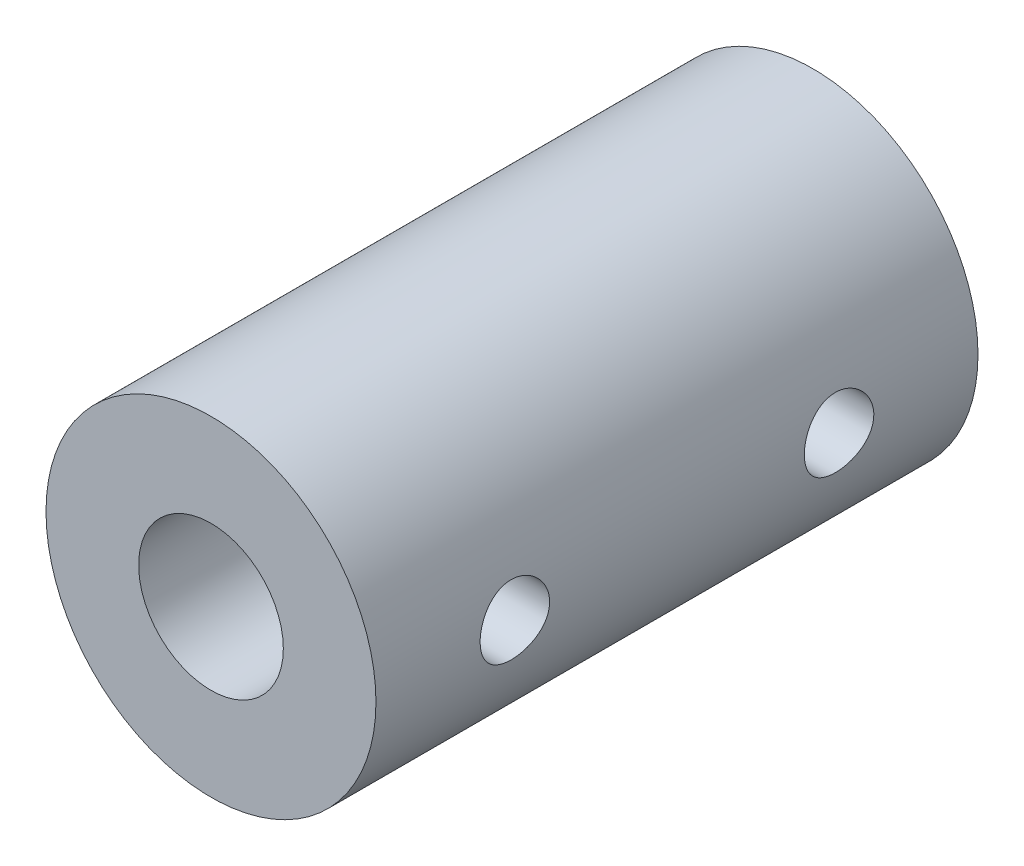
SolidWorks part; units mm, degrees
ref_plane "Front Plane" through (0, 0, 0) normal (0, 0, 1) x (1, 0, 0)
ref_plane "Top Plane" through (0, 0, 0) normal (0, 1, 0) x (1, 0, 0)
ref_plane "Right Plane" through (0, 0, 0) normal (1, 0, 0) x (0, 0, -1)
sketch "Sketch1" plane through (0, 0, 0) normal (0, 0, 1) x (1, 0, 0)
  circle A0 centre (-9.4185, 11.8755) radius 3.125
  circle A1 centre (-9.4185, 11.8755) radius 7.125
  dimension "D1" = 6.25
  dimension "D2" = 14.25
extrude "Boss-Extrude1" add sketch "Sketch1" along normal blind 13 and the other way blind 13
sketch "Sketch2" plane through (0, 0, 0) normal (1, 0, 0) x (0, 0, -1)
  line L2 (0, 7.2875) -> (0, -7.2875) construction
  circle A0 centre (-7, 11.8755) radius 1.5
  dimension "D1" = 3
  dimension "D2" = 7
extrude "Cut-Extrude1" cut sketch "Sketch2" against normal blind 20
mirror "Mirror1" about plane through (0, 0, 0) normal (0, 0, 1) of "Cut-Extrude1"
